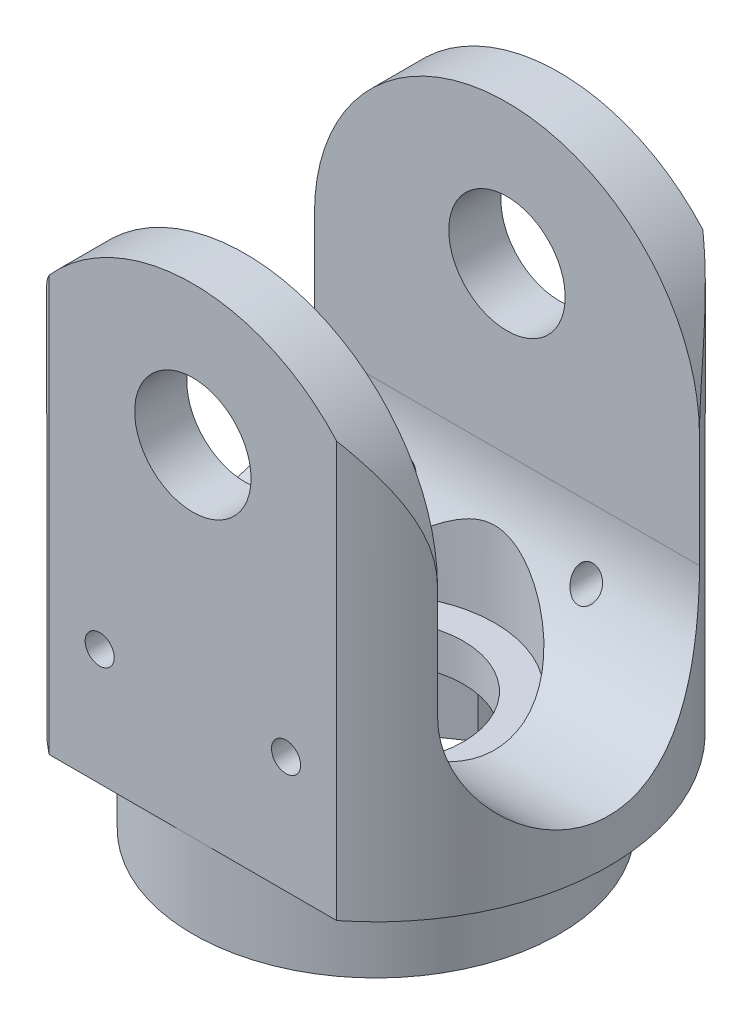
SolidWorks part; units mm, degrees
material "7075-T6 (SN)"
ref_plane "X-Y Datum" through (0, 0, 0) normal (0, 0, 1) x (1, 0, 0)
ref_plane "X-Z Datum" through (0, 0, 0) normal (0, 1, 0) x (1, 0, 0)
ref_plane "Y-Z Datum" through (0, 0, 0) normal (1, 0, 0) x (0, 0, -1)
sketch "Sketch1" plane through (0, 0, 0) normal (0, 1, 0) x (1, 0, 0)
  circle A0 centre (0, 0) radius 12.7
  dimension "D1" = 25.4
extrude "Boss-Extrude1" add sketch "Sketch1" along normal blind 15.367 and the other way blind 15.367
ref_plane "Plane2" through (0, 0, 9.9886) normal (0, 0, 1) x (1, 0, 0)
sketch "Sketch4" plane through (0, 0, 9.9886) normal (0, 0, 1) x (1, 0, 0)
  line L1 (-12.7, 15.367) -> (12.7, 15.367)
  line L2 (-12.7, 15.367) -> (-12.7, -15.367)
  line L3 (-12.7, -15.367) -> (12.7, -15.367)
  line L4 (12.7, 15.367) -> (12.7, -15.367)
extrude "Cut-Extrude2" cut sketch "Sketch4" along normal through all
mirror "Mirror2" about plane through (0, 0, 0) normal (0, 0, 1) of "Cut-Extrude2"
sketch "Sketch5" plane through (0, 0, 0) normal (1, 0, 0) x (0, 0, -1)
  line L0 (9.9886, 15.367) -> (-9.9886, 15.367) construction
  line L1 (-7.1437, 15.367) -> (7.1437, 15.367)
  line L2 (-7.1437, 15.367) -> (-7.1437, -1.27)
  line L3 (-7.1437, -1.27) -> (7.1438, -1.27)
  line L4 (7.1437, 15.367) -> (7.1438, -1.27)
  line L5 (0, 13.97) -> (0, -13.97) construction
  line L6 (0, -8.4138) -> (0, 15.367) construction
  arc A0 (-7.1437, -1.27) -> (7.1438, -1.27) centre (0, -1.27) ccw
  dimension "D3" = 16.637
  dimension "D4" = 23.7808
  dimension "D1" = 14.2875
  dimension "D2" = 7.1437
extrude "Cut-Extrude3" cut sketch "Sketch5" against normal through all both and the other way through all contours L6 A0 L3 | A0 L6 L3 | L2 L1 L4 L3 region at (0, -4.3019, 3.0319) region at (0, -4.3019, -3.0319)
sketch "Sketch6" plane through (0, 0, 9.9886) normal (0, 0, 1) x (1, 0, 0)
  line L0 (0, -43.0151) -> (0, 43.0151) construction
  line L1 (-7.8434, 15.367) -> (7.8434, 15.367) construction
  line L2 (10.5004, 4.8666) -> (14.8497, 4.8666)
  line L3 (-10.5004, 4.8666) -> (-14.8497, 4.8666)
  circle A0 centre (0, 4.8666) radius 10.5004
  arc A1 (14.8497, 4.8666) -> (-14.8497, 4.8666) centre (0, 4.8666) ccw
  line M2 (7.8434, 15.367) -> (-7.8434, 15.367)
  line M3 (-7.8434, 15.367) -> (-7.8434, -15.367)
  line M5 (7.8434, -15.367) -> (7.8434, 15.367)
  dimension "D1" = 21.0007
extrude "Cut-Extrude4" cut sketch "Sketch6" against normal through all contours L2 A1 L3 A0 M3 M2 M5 | A0 M2 M3 | A0 M5 M2 region at (10.124, 8.7197, 9.9886) region at (5.9543, 14.3505, 9.9886) region at (-5.9543, 14.3505, 9.9886)
sketch "Sketch7" plane through (0, -15.367, 0) normal (0, -1, 0) x (1, 0, 0)
  circle A0 centre (0, 0) radius 4.7625
  dimension "D1" = 9.525
extrude "Cut-Extrude5" cut sketch "Sketch7" against normal through all
sketch "Sketch9" plane through (0, -15.367, 0) normal (0, -1, 0) x (1, 0, 0)
  circle A0 centre (0, 0) radius 9.9822
  circle A1 centre (0, 0) radius 17.8528
  dimension "D1" = 19.9644
extrude "Cut-Extrude6" cut sketch "Sketch9" against normal blind 4.572
ref_plane "Plane3" through (0, 15.367, 0) normal (0, 1, 0) x (1, 0, 0)
sketch "Sketch10" plane through (0, 15.367, 0) normal (0, 1, 0) x (1, 0, 0)
  circle A0 centre (0, 0) radius 6.477
  dimension "D1" = 12.954
extrude "Cut-Extrude7" cut sketch "Sketch10" against normal blind 24.257
sketch "Sketch11" plane through (0, 0, 9.9886) normal (0, 0, 1) x (1, 0, 0)
  line L0 (-9.9822, -10.795) -> (9.9822, -10.795) construction
  line L1 (0, 7.747) -> (0, 0) construction
  circle A0 centre (0, 7.747) radius 3.175
  dimension "D1" = 6.35
  dimension "D2" = 18.542
extrude "Cut-Extrude8" cut sketch "Sketch11" against normal through all
sketch "Sketch12" plane through (0, 0, -9.9886) normal (0, 0, -1) x (-1, 0, 0)
  line L0 (-7.8434, -10.795) -> (7.8434, -10.795) construction
  line L1 (7.8434, 11.848) -> (7.8434, -10.795) construction
  line L2 (-7.8434, -10.795) -> (-7.8434, 11.848) construction
  circle A0 centre (5.0811, -4.445) radius 0.7938
  circle A1 centre (-5.0811, -4.445) radius 0.7938
  point P6 (-5.8749, -4.445)
  point P7 (5.8749, -4.445)
  dimension "D1" = 1.5875
  dimension "D2" = 1.5875
  dimension "D3" = 6.35
  dimension "D4" = 6.35
  dimension "D5" = 1.9685
  dimension "D6" = 1.9685
extrude "Cut-Extrude9" cut sketch "Sketch12" against normal through all both and the other way through all
sketch "Sketch13" plane through (0, -15.367, 0) normal (0, -1, 0) x (1, 0, 0)
  line L0 (-0.2399, -7.9974) -> (7.5971, -2.5099)
  line L1 (4.5892, -6.554) -> (0, 0) construction
  line L2 (-2.6525, 0) -> (2.3493, 0)
  circle A0 centre (0, 0) radius 8.001
  dimension "D1" = 16.002
  dimension "D2" = 35
  dimension "D3" = 6.4135
extrude "Cut-Extrude10" [suppressed] cut sketch "Sketch13" against normal blind 4.445
sketch "Sketch14" [suppressed] plane through (0, -15.367, 0) normal (0, -1, 0) x (1, 0, 0)
  line L0 (0, 0) -> (-0.2399, -7.9974) construction
  line L1 (0, 0) -> (7.5971, -2.5099) construction
  circle A0 centre (-0.217, -7.2354) radius 1.5875
  circle A1 centre (6.8736, -2.2708) radius 1.5875
  dimension "D1" = 3.175
  dimension "D2" = 3.175
  dimension "D3" = 0.762
  dimension "D4" = 0.762
extrude "Cut-Extrude11" [suppressed] cut sketch "Sketch14" against normal up to surface (4.445 mm away) up to face at (0, -15.367, -4.7625)
sketch "Sketch15" plane through (0, -15.367, 0) normal (0, -1, 0) x (1, 0, 0)
  line L0 (-7.5971, -2.5099) -> (0.2399, -7.9974)
  line L1 (-4.5892, -6.554) -> (0, 0) construction
  line L2 (0.0088, 0) -> (5.0106, 0)
  circle A0 centre (0, 0) radius 8.001
  circle A1 centre (0, 0) radius 9.9822 construction
  dimension "D3" = 16.002
  dimension "D1" = 35
  dimension "D2" = 6.4135
extrude "Cut-Extrude12" cut sketch "Sketch15" against normal blind 4.445 contours L0 A0 region at (0.2194, -15.367, 0.3134)
sketch "Sketch16" plane through (0, -15.367, 0) normal (0, -1, 0) x (1, 0, 0)
  line L0 (0, 0) -> (-7.5971, -2.5099) construction
  line L1 (0, 0) -> (0.2399, -7.9974) construction
  circle A0 centre (-6.8736, -2.2708) radius 1.5875
  circle A1 centre (0.217, -7.2354) radius 1.5875
  dimension "D1" = 3.175
  dimension "D2" = 0.762
  dimension "D3" = 0.762
extrude "Cut-Extrude13" cut sketch "Sketch16" against normal up to surface (4.445 mm away) up to face at (0, -10.922, -4.7625)
sketch "Pick Up Point" plane through (0, 0, 0) normal (0, 0, 1) x (1, 0, 0)
  point P0 (0, 7.747)
ref_plane "Plane4" through (0, 15.367, -7.1437) normal (0, 1, 0) x (1, 0, 0)
sketch "Sketch20" plane through (0, 15.367, -7.1437) normal (0, 1, 0) x (1, 0, 0)
  circle A0 centre (0, -7.1437) radius 12.7
  point P3 (0, 5.5562)
  point P4 (0, -19.8438)
  point P6 (0, -7.1437)
  dimension "D1" = 25.4
ref_plane "Plane5" through (0, -15.367, 0) normal (0, -1, 0) x (-1, 0, 0)
sketch "Sketch21" plane through (0, -15.367, 0) normal (0, -1, 0) x (-1, 0, 0)
  point P0 (0, 0)
ref_point "Point1"
ref_point "Point2"
ref_point "Point3"
ref_point "Point4"
sketch "Sketch19" plane through (0, -10.922, 0) normal (0, -1, 0) x (1, 0, 0)
  line L0 (1.693, -7.8198) -> (-7.9273, -1.0834) construction
  arc A0 (1.693, -7.8198) -> (-7.9273, -1.0834) centre (0, 0) ccw construction
ref_point "Point5"
ref_axis "Axis1" through (0, -10.922, 0) along (0, -1, 0)
sketch "Sketch22" plane through (0, 0, 9.9886) normal (0, 0, 1) x (1, 0, 0)
  arc A0 (7.8434, 11.848) -> (-7.8434, 11.848) centre (0, 4.8666) ccw construction
  point P0 (0, 15.367)
sketch3d "3DSketch1"
  line L0 (0, 7.747, 9.9886) -> (0, 7.747, -9.9886) construction
  line L1 (0, 7.747, 7.1437) -> (0, 7.747, 9.9886) construction
  line L2 (0, 7.747, -9.9886) -> (0, 7.747, -7.1438) construction
  point P6 (0, 7.747, 0)
